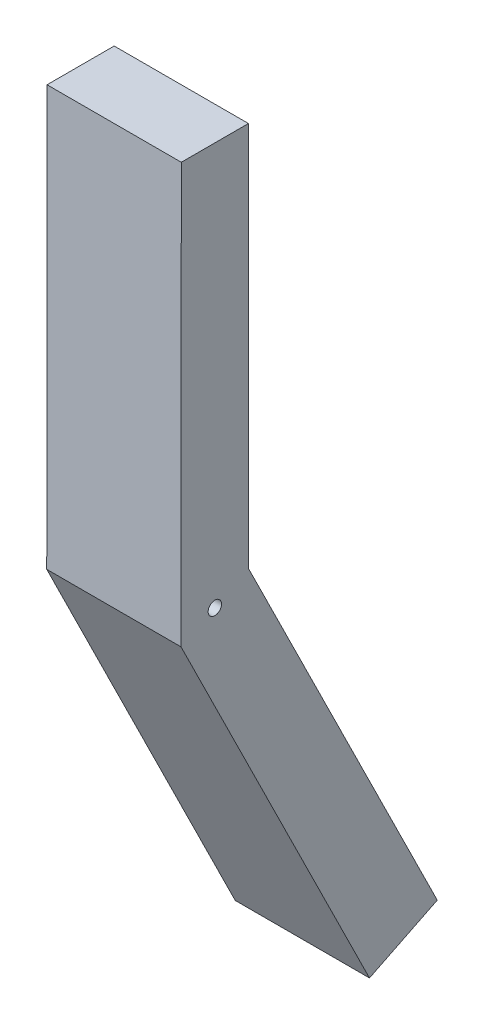
SolidWorks part; units mm, degrees
ref_plane "Plan de face" through (0, 0, 0) normal (0, 0, 1) x (1, 0, 0)
ref_plane "Plan de dessus" through (0, 0, 0) normal (0, 1, 0) x (1, 0, 0)
ref_plane "Plan de droite" through (0, 0, 0) normal (1, 0, 0) x (0, 0, -1)
sketch "Esquisse1" plane through (0, 0, 0) normal (1, 0, 0) x (0, 0, -1)
  line L5 (-5, -60) -> (5, 60) construction
  line L6 (-5, 60) -> (5, -60) construction
  line L10 (23.0381, -59.2708) -> (5.0478, 2.4972) construction
  line L11 (-5.0478, -2.4972) -> (33.1337, -54.2765) construction
  line L12 (5.0478, 2.4972) -> (33.1337, -54.2765)
  line L13 (23.0381, -59.2708) -> (-5.0478, -2.4972)
  line L14 (-5, 60) -> (5, 60)
  line L15 (-5.0478, -2.4972) -> (-5, 60)
  line L16 (5, 60) -> (5.0478, 2.4972)
  line L17 (23.0381, -59.2708) -> (33.1337, -54.2765)
  circle A0 centre (0, 0) radius 1
  point P0 (0, 0)
  point P9 (14.0429, -28.3868)
  dimension "D3" = 2
  dimension "D1" = 120
  dimension "D2" = 10
extrude "Boss.-Extru.1" add sketch "Esquisse1" along normal blind 10 and the other way blind 10
